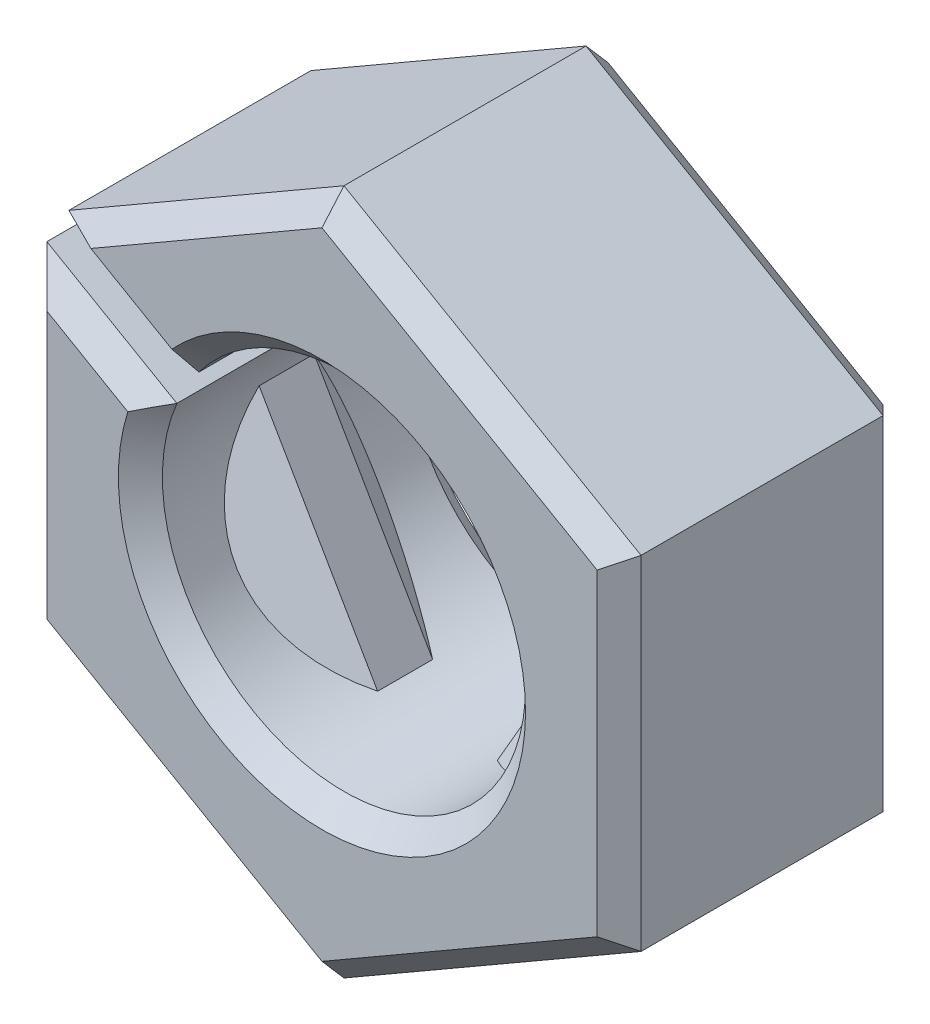
SolidWorks part; units mm, degrees
ref_plane "Front" through (0, 0, 0) normal (0, 0, 1) x (1, 0, 0)
ref_plane "Top" through (0, 0, 0) normal (0, 1, 0) x (1, 0, 0)
ref_plane "Right" through (0, 0, 0) normal (1, 0, 0) x (0, 0, -1)
sketch "Sketch1" plane through (0, 0, 0) normal (0, 0, 1) x (1, 0, 0)
  line L1 (2.7, -1.5588) -> (2.7, 1.5588)
  line L2 (2.7, 1.5588) -> (0, 3.1177)
  line L3 (0, 3.1177) -> (-2.7, 1.5588)
  line L4 (-2.7, 1.5588) -> (-2.7, -1.5588)
  line L5 (-2.7, -1.5588) -> (0, -3.1177)
  line L6 (0, -3.1177) -> (2.7, -1.5588)
  circle A0 centre (0, 0) radius 2.7 construction
  circle A1 centre (0, 0) radius 1.65
  dimension "D1" = 3.3
  dimension "D2" = 5.4
extrude "Boss-Extrude1" add sketch "Sketch1" along normal mid plane 2.6
sketch "Sketch3" plane through (0, 0, 0) normal (1, 0, 0) x (0, 0, -1)
  line L0 (-0.65, 1.65) -> (0.65, 1.65)
  line L1 (1.3, 1.65) -> (-1.3, 1.65) construction
  line L4 (0, 0) -> (0, 1.25) construction
  line L5 (0.65, 1.65) -> (0.25, 1.25)
  line L6 (0.25, 1.25) -> (-0.25, 1.25)
  line L7 (-0.25, 1.25) -> (-0.65, 1.65)
  dimension "D1" = 0.4
  dimension "D2" = 90
  dimension "D3" = 0.5
extrude "Clip" add sketch "Sketch3" along normal up to next and the other way up to next
pattern_circular "Clips x3" count 3 over 360 about axis through (0, 0, 1.3) along (0, 0, 1) of "Clip"
sketch "Sketch4" plane through (0, 0, 0) normal (0, 0, 1) x (1, 0, 0)
  line L0 (-2.7, 1.5588) -> (0, 0)
extrude "Split" cut sketch "Sketch4" against normal through all both and the other way through all thin thin type mid plane wall 0.4
chamfer "Deburs" distance 0.2 angle 45 18 edges at (1.4289, -0.825, -1.3) (2.7, 0, -1.3) (1.35, 2.3383, -1.3) (-1.25, 2.396, -1.3) (-2.7, -0.1155, -1.3) (-1.35, -2.3383, -1.3) (1.35, -2.3383, -1.3) (1.4289, -0.825, 1.3) (-1.35, -2.3383, 1.3) (-2.7, -0.1155, 1.3) (-1.25, 2.396, 1.3) (1.35, 2.3383, 1.3) (2.7, 0, 1.3) (1.35, -2.3383, 1.3) (-1.9092, 1.3332, -1.3) (-2.1092, 0.9868, -1.3) (-1.9092, 1.3332, 1.3) (-2.1092, 0.9868, 1.3)
equation "\"D1@Sketch1\"=\"Hardware Clearance Hole Diameter@Box Assy.Assembly\"+.15"
equation "\"D2@Sketch1\"=\"Nut Trap Diameter@Box Assy.Assembly\"-0.3mm"
equation "\"D1@Boss-Extrude1\"=\"Nut Trap Depth@Box Assy.Assembly\""
